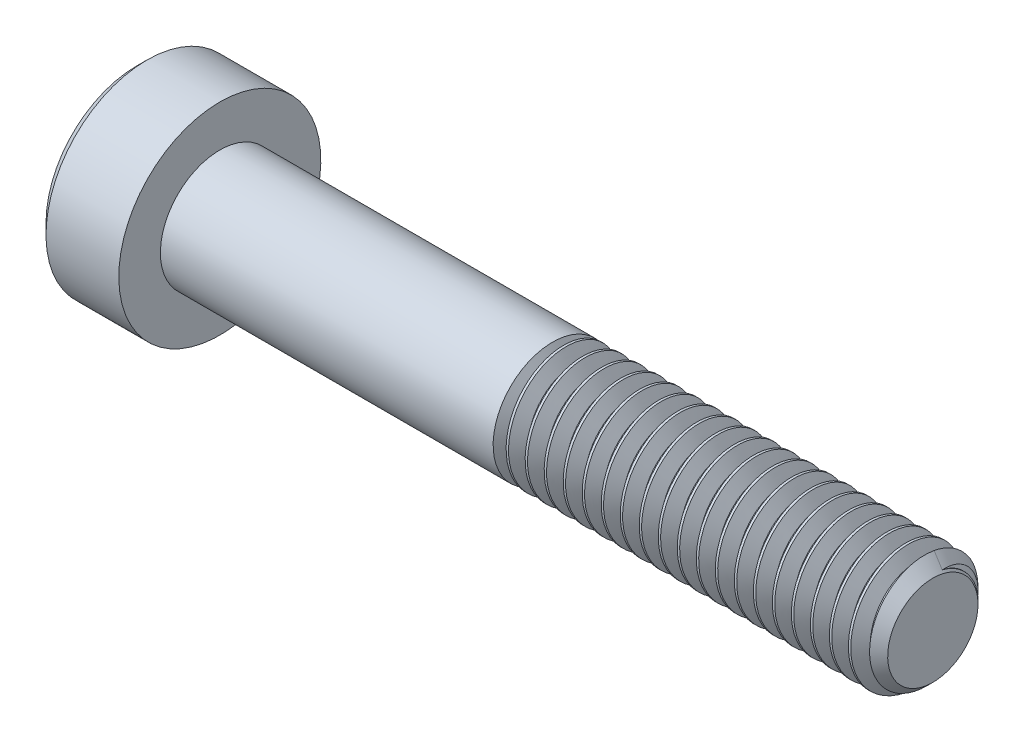
SolidWorks part; units mm, degrees
ref_plane "Front Plane" through (0, 0, 0) normal (0, 0, 1) x (1, 0, 0)
ref_plane "Top Plane" through (0, 0, 0) normal (0, 1, 0) x (1, 0, 0)
ref_plane "Right Plane" through (0, 0, 0) normal (1, 0, 0) x (0, 0, -1)
sketch "Sketch1" plane through (0, 0, 0) normal (0, 0, 1) x (1, 0, 0)
  line L0 (15, 0) -> (-15, 0) construction
  line L1 (15, 2.5) -> (15, -2.5) construction
  line L2 (-15, 4.25) -> (-15, -4.25) construction
  line L3 (-15, 4.25) -> (-18.0625, 4.25) construction
  line L4 (-18.0625, 4.25) -> (-18.5, 3.8125) construction
  line L5 (-18.5, 3.8125) -> (-18.5, -3.8125) construction
  line L6 (-18.5, -3.8125) -> (-18.0625, -4.25) construction
  line L7 (-18.0625, -4.25) -> (-15, -4.25) construction
  line L8 (-1, 2.5) -> (-1, -2.5) construction
  point P7 (-15.68, 0)
  point P12 (11.8, -2.5)
  dimension "D1" = 45
  dimension "Dec." = 5
  dimension "Length" = 30
  dimension "Head Dia" = 8.5
  dimension "Head Height" = 3.5
  dimension "Hex Depth" = 2.82
  dimension "Chamfer" = 0.4375
  dimension "D2" = 3.2
  dimension "Thread Length" = 16
ref_plane "Plane1" through (15, 0, 0) normal (1, 0, 0) x (0, 0, -1)
ref_plane "Plane2" through (-18.5, 0, 0) normal (1, 0, 0) x (0, 0, -1)
sketch "Sketch2" plane through (15, 0, 0) normal (1, 0, 0) x (0, 0, -1)
  circle A0 centre (0, 0) radius 2.5
extrude "Boss-Extrude1" add sketch "Sketch2" against normal up to vertex (16 mm away) up to point (-1, 2.5, 0)
sketch "Sketch3" plane through (15, 0, 0) normal (1, 0, 0) x (0, 0, -1)
  circle A0 centre (0, 0) radius 2.5 construction
  circle A1 centre (0, 0) radius 2.5
curve "Helix/Spiral1" pitch 0.8 height 16.8 radius 2.5 centre (15, 0, 0) axis (-1, 0, 0) start towards (0, 1, 0) parameters "Pitch"=0.8
chamfer "Chamfer1" distance 0.6 angle 45 1 edges at (15, 0, -2.5)
sketch "Sketch5" plane through (0, 0, 0) normal (0, 0, 1) x (1, 0, 0)
  line L0 (14.65, 2.5) -> (15.35, 2.5)
  line L1 (15.35, 2.5) -> (15.05, 1.9804)
  line L2 (15.05, 1.9804) -> (14.95, 1.9804)
  line L3 (14.95, 1.9804) -> (14.65, 2.5)
  line L4 (15, 1.9804) -> (15, 2.5) construction
  line L5 (14.8, 2.2402) -> (15.2, 2.2402) construction
  dimension "D1" = 60
  dimension "D2" = 0.4
  dimension "D3" = 0.1
sweep "Cut-Sweep1" cut profiles "Sketch5" path "Helix/Spiral1" align with end faces yes
sketch "Sketch4" plane through (-18.5, 0, 0) normal (1, 0, 0) x (0, 0, -1)
  line L0 (-4.25, 0.7937) -> (4.25, 0.7937) construction
  line L1 (0, 1.7321) -> (-1.5, 0.866)
  line L2 (-1.5, 0.866) -> (-1.5, -0.866)
  line L3 (-1.5, -0.866) -> (0, -1.7321)
  line L4 (0, -1.7321) -> (1.5, -0.866)
  line L5 (1.5, -0.866) -> (1.5, 0.866)
  line L6 (1.5, 0.866) -> (0, 1.7321)
  line L7 (0, 0) -> (0, 0.7937) construction
  circle A0 centre (0, 0) radius 1.5 construction
  dimension "Hex Size" = 3
  dimension "D1" = 8.5
  dimension "D2" = 0.7937
sketch "Sketch10" plane through (0, 0, 0) normal (0, 0, 1) x (1, 0, 0)
  line L0 (-15, 0) -> (0.4434, 0) construction
  line L1 (0.4434, 0) -> (-1, 2.5)
  line L2 (-1, 2.5) -> (-15, 2.5)
  line L3 (-15, 2.5) -> (-15, 0)
  line L4 (-15, 4.25) -> (-15, -4.25) construction
  line L5 (-15, 0) -> (0.4434, 0)
  dimension "D1" = 60
revolve "Revolve2" add sketch "Sketch10" angle 360 about L0
sketch "Sketch6" plane through (0, 0, 0) normal (0, 0, 1) x (1, 0, 0)
  line L0 (-18.0625, 4.25) -> (-18.5, 3.8125) construction
  line L1 (-15, 4.25) -> (-18.0625, 4.25) construction
  line L2 (-15, 4.25) -> (-15, -4.25) construction
  line L3 (-18.5, 3.8125) -> (-18.5, -3.8125) construction
  line L4 (-18.0625, 4.25) -> (-18.5, 3.8125)
  line L5 (-15, 4.25) -> (-18.0625, 4.25)
  line L6 (-15, 4.25) -> (-15, 0)
  line L7 (-18.5, 3.8125) -> (-18.5, 0)
  line L8 (-15, 0) -> (-18.5, 0) construction
  line L9 (-15, 0) -> (-18.5, 0)
revolve "Revolve1" add sketch "Sketch6" angle 360 about L8
extrude "Cut-Extrude1" cut sketch "Sketch4" along normal up to vertex (2.82 mm away) up to point (-15.68, 0, 0)
sketch "Sketch8" plane through (-18.5, 0, 0) normal (-1, 0, 0) x (0, 0, 1)
  circle A1 centre (0, 0) radius 1.7321
extrude "Cut-Extrude2" cut sketch "Sketch8" against normal through all draft 45
equation "\"D3@Helix/Spiral1\" = \"Thread Length@Sketch1\"+\"Pitch@Helix/Spiral1\""
equation "\"D3@Sketch5\" = \"Pitch@Helix/Spiral1\"*.125"
equation "\"D2@Sketch5\" = \"Pitch@Helix/Spiral1\"*.50"
equation "\"D1@Chamfer1\" = \"Pitch@Helix/Spiral1\"*.75"
equation "\"D2@Sketch1\" = \"Pitch@Helix/Spiral1\"*4"
equation "\"D1@Sketch4\" = \"Head Dia@Sketch1\""
equation "\"Chamfer@Sketch1\" = \"Head Height@Sketch1\"/8"
